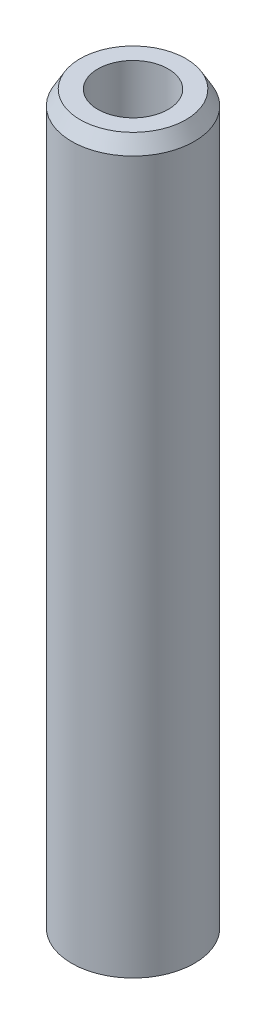
SolidWorks part; units mm, degrees
ref_plane "Front Plane" through (0, 0, 0) normal (0, 0, 1) x (1, 0, 0)
ref_plane "Top Plane" through (0, 0, 0) normal (0, 1, 0) x (1, 0, 0)
ref_plane "Right Plane" through (0, 0, 0) normal (1, 0, 0) x (0, 0, -1)
sketch "Sketch1" plane through (0, 0, 0) normal (0, 1, 0) x (1, 0, 0)
  circle A0 centre (0, 0) radius 7.5
  dimension "SHAFT_OD" = 15
extrude "Boss-Extrude1" add sketch "Sketch1" along normal blind 89.8381
sketch "Sketch2" plane through (0, 0, 0) normal (0, 1, 0) x (1, 0, 0)
  circle A0 centre (0, 0) radius 4.299
  dimension "BORE_D" = 8.598
extrude "Cut-Extrude1" cut sketch "Sketch2" along normal through all
chamfer "Chamfer1" distance 1.7844 angle 30 2 edges at (0, 89.8381, 7.5) (0, 0, 7.5) first distance on face at (0, 89.8381, 7.5) first distance on face at (0, 0, 4.299)
